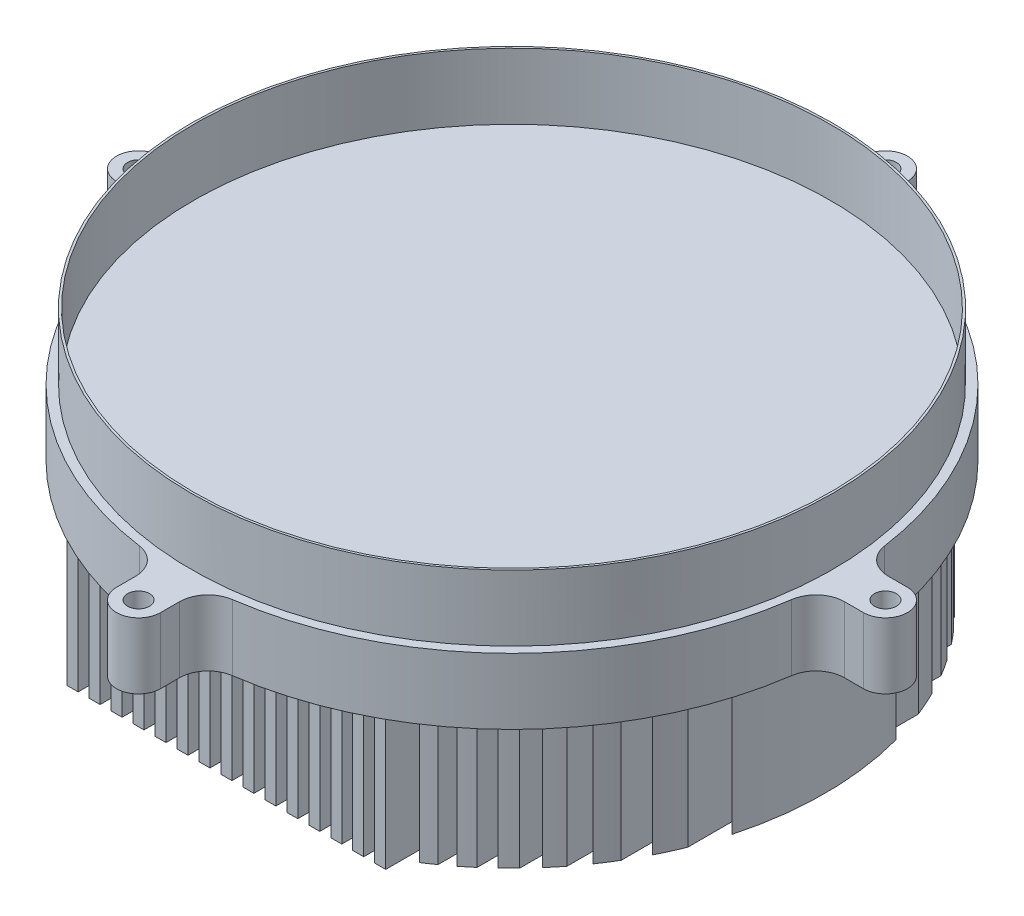
SolidWorks part; units mm, degrees
ref_plane "Front Plane" through (0, 0, 0) normal (0, 0, 1) x (1, 0, 0)
ref_plane "Top Plane" through (0, 0, 0) normal (0, 1, 0) x (1, 0, 0)
ref_plane "Right Plane" through (0, 0, 0) normal (1, 0, 0) x (0, 0, -1)
sketch "Sketch2" plane through (0, 0, 0) normal (0, 1, 0) x (1, 0, 0)
  line L0 (0, 0) -> (0, -224.3017) construction
  line L1 (0, 0) -> (0, 200) construction
  line L2 (0, 0) -> (207.2583, 0) construction
  line L3 (0, 0) -> (-200, 0) construction
  line L4 (20, 148.6607) -> (20, 168.6607)
  line L5 (-20, 148.6607) -> (-20, 168.6607)
  line L6 (148.6607, 20) -> (168.6607, 20)
  line L7 (148.6607, -20) -> (168.6607, -20)
  line L8 (20, -148.6607) -> (20, -168.6607)
  line L9 (-20, -148.6607) -> (-20, -168.6607)
  line L10 (-148.6607, -20) -> (-168.6607, -20)
  line L11 (-148.6607, 20) -> (-168.6607, 20)
  circle A0 centre (0, 0) radius 146
  circle A1 centre (0, 0) radius 145
  arc A3 (-20, 168.6607) -> (20, 168.6607) centre (0, 168.6607) cw
  circle A4 centre (0, 168.6607) radius 4.3737
  arc A5 (168.6607, 20) -> (168.6607, -20) centre (168.6607, 0) cw
  circle A6 centre (168.6607, 0) radius 4.3737
  arc A7 (20, -168.6607) -> (-20, -168.6607) centre (0, -168.6607) cw
  circle A8 centre (0, -168.6607) radius 4.3737
  arc A9 (-168.6607, -20) -> (-168.6607, 20) centre (-168.6607, 0) cw
  circle A10 centre (-168.6607, 0) radius 4.3737
  point P36 (0, 0)
  dimension "D1" = 290
  dimension "D2" = 292
  dimension "D4" = 4
extrude "Boss-Extrude2" add sketch "Sketch2" along normal blind 30 contours A1 | A0
sketch "Sketch3" plane through (0, 0, 0) normal (0, 1, 0) x (1, 0, 0)
  line L0 (0, 0) -> (211.9111, 0) construction
  line L1 (0, 0) -> (-205.2426, 0) construction
  line L2 (0, 0) -> (0, 170) construction
  line L3 (0, 0) -> (0, -200) construction
  line L4 (161.3691, 10) -> (170, 10)
  line L5 (161.3691, -10) -> (170, -10)
  line L6 (-10, 161.3691) -> (-10, 170)
  line L7 (10, 161.3691) -> (10, 170)
  line L8 (10, -161.3691) -> (10, -170)
  line L9 (-10, -161.3691) -> (-10, -170)
  line L10 (-161.3691, -10) -> (-170, -10)
  line L11 (-161.3691, 10) -> (-170, 10)
  arc A0 (-21.1656, 148.4992) -> (-148.4992, 21.1656) centre (0, 0) ccw
  circle A1 centre (0, 170) radius 5
  arc A2 (-10, 170) -> (10, 170) centre (0, 170) cw
  arc A3 (10, 161.3691) -> (21.1656, 148.4992) centre (23, 161.3691) ccw
  arc A4 (-10, 161.3691) -> (-21.1656, 148.4992) centre (-23, 161.3691) cw
  arc A5 (170, 10) -> (170, -10) centre (170, 0) cw
  arc A6 (161.3691, 10) -> (148.4992, 21.1656) centre (161.3691, 23) cw
  circle A7 centre (170, 0) radius 5
  arc A8 (161.3691, -10) -> (148.4992, -21.1656) centre (161.3691, -23) ccw
  arc A9 (10, -170) -> (-10, -170) centre (0, -170) cw
  arc A10 (10, -161.3691) -> (21.1656, -148.4992) centre (23, -161.3691) cw
  circle A11 centre (0, -170) radius 5
  arc A12 (-10, -161.3691) -> (-21.1656, -148.4992) centre (-23, -161.3691) ccw
  arc A13 (-170, -10) -> (-170, 10) centre (-170, 0) cw
  arc A14 (-161.3691, -10) -> (-148.4992, -21.1656) centre (-161.3691, -23) cw
  circle A15 centre (-170, 0) radius 5
  arc A16 (-161.3691, 10) -> (-148.4992, 21.1656) centre (-161.3691, 23) ccw
  arc A17 (-148.4992, -21.1656) -> (-21.1656, -148.4992) centre (0, 0) ccw
  arc A18 (148.4992, 21.1656) -> (21.1656, 148.4992) centre (0, 0) ccw
  arc A19 (21.1656, -148.4992) -> (148.4992, -21.1656) centre (0, 0) ccw
  point P53 (0, 0)
  dimension "D1" = 300
  dimension "D4" = 10
  dimension "D2" = 4
extrude "Boss-Extrude4" add sketch "Sketch3" against normal blind 30
sketch "Sketch4" plane through (0, -30, 0) normal (0, 1, 0) x (1, 0, 0)
  line L0 (0, 0) -> (0, 214.2399) construction
  line L1 (0, 0) -> (0, -238.4864) construction
  line L2 (0, 0) -> (-208.9775, 0) construction
  line L3 (0, 0) -> (218.7408, 0) construction
  line L4 (2.5, 130) -> (-2.5, 130)
  line L5 (-2.5, 130) -> (-2.5, -130)
  line L6 (2.5, 130) -> (2.5, -130)
  line L7 (2.5, -130) -> (-2.5, -130)
  line L8 (12.5, 130) -> (12.5, -130)
  line L9 (12.5, 130) -> (7.5, 130)
  line L10 (7.5, 130) -> (7.5, -130)
  line L11 (12.5, -130) -> (7.5, -130)
  line L12 (22.5, 130) -> (22.5, -130)
  line L13 (22.5, 130) -> (17.5, 130)
  line L14 (17.5, 130) -> (17.5, -130)
  line L15 (22.5, -130) -> (17.5, -130)
  line L16 (32.5, 130) -> (32.5, -130)
  line L17 (32.5, 130) -> (27.5, 130)
  line L18 (27.5, 130) -> (27.5, -130)
  line L19 (32.5, -130) -> (27.5, -130)
  line L20 (42.5, 130) -> (42.5, -130)
  line L21 (42.5, 130) -> (37.5, 130)
  line L22 (37.5, 130) -> (37.5, -130)
  line L23 (42.5, -130) -> (37.5, -130)
  line L24 (52.5, 130) -> (52.5, -130)
  line L25 (52.5, 130) -> (47.5, 130)
  line L26 (47.5, 130) -> (47.5, -130)
  line L27 (52.5, -130) -> (47.5, -130)
  line L28 (62.5, 130) -> (62.5, -130)
  line L29 (62.5, 130) -> (57.5, 130)
  line L30 (57.5, 130) -> (57.5, -130)
  line L31 (62.5, -130) -> (57.5, -130)
  line L32 (72.5, 130) -> (72.5, -130)
  line L33 (72.5, 130) -> (67.5, 130)
  line L34 (67.5, 130) -> (67.5, -130)
  line L35 (72.5, -130) -> (67.5, -130)
  line L36 (82.5, 116.1895) -> (82.5, -116.1895)
  line L38 (77.5, 119.5826) -> (77.5, -119.5826)
  line L40 (92.5, 108.3974) -> (92.5, -108.3974)
  line L42 (87.5, 112.4722) -> (87.5, -112.4722)
  line L44 (102.5, 98.9949) -> (102.5, -98.9949)
  line L46 (97.5, 103.923) -> (97.5, -103.923)
  line L48 (112.5, 87.4643) -> (112.5, -87.4643)
  line L50 (107.5, 93.5414) -> (107.5, -93.5414)
  line L52 (-7.5, 130) -> (-12.5, 130)
  line L53 (-12.5, 130) -> (-12.5, -130)
  line L54 (-7.5, 130) -> (-7.5, -130)
  line L55 (-7.5, -130) -> (-12.5, -130)
  line L56 (-17.5, 130) -> (-22.5, 130)
  line L57 (-22.5, 130) -> (-22.5, -130)
  line L58 (-17.5, 130) -> (-17.5, -130)
  line L59 (-17.5, -130) -> (-22.5, -130)
  line L60 (-27.5, 130) -> (-32.5, 130)
  line L61 (-32.5, 130) -> (-32.5, -130)
  line L62 (-27.5, 130) -> (-27.5, -130)
  line L63 (-27.5, -130) -> (-32.5, -130)
  line L64 (-37.5, 130) -> (-42.5, 130)
  line L65 (-42.5, 130) -> (-42.5, -130)
  line L66 (-37.5, 130) -> (-37.5, -130)
  line L67 (-37.5, -130) -> (-42.5, -130)
  line L68 (-47.5, 130) -> (-52.5, 130)
  line L69 (-52.5, 130) -> (-52.5, -130)
  line L70 (-47.5, 130) -> (-47.5, -130)
  line L71 (-47.5, -130) -> (-52.5, -130)
  line L72 (-57.5, 130) -> (-62.5, 130)
  line L73 (-62.5, 130) -> (-62.5, -130)
  line L74 (-57.5, 130) -> (-57.5, -130)
  line L75 (-57.5, -130) -> (-62.5, -130)
  line L76 (-67.5, 130) -> (-72.5, 130)
  line L77 (-72.5, 130) -> (-72.5, -130)
  line L78 (-67.5, 130) -> (-67.5, -130)
  line L79 (-67.5, -130) -> (-72.5, -130)
  line L81 (-82.5, 116.1895) -> (-82.5, -116.1895)
  line L82 (-77.5, 119.5826) -> (-77.5, -119.5826)
  line L85 (-92.5, 108.3974) -> (-92.5, -108.3974)
  line L86 (-87.5, 112.4722) -> (-87.5, -112.4722)
  line L89 (-102.5, 98.9949) -> (-102.5, -98.9949)
  line L90 (-97.5, 103.923) -> (-97.5, -103.923)
  line L93 (-112.5, 87.4643) -> (-112.5, -87.4643)
  line L94 (-107.5, 93.5414) -> (-107.5, -93.5414)
  line L97 (-122.5, 72.8011) -> (-122.5, -72.8011)
  line L98 (-117.5, 80.6226) -> (-117.5, -80.6226)
  line L101 (-132.5, 52.4404) -> (-132.5, -52.4404)
  line L102 (-127.5, 63.6396) -> (-127.5, -63.6396)
  line L106 (-137.5, 37.4166) -> (-137.5, -37.4166)
  line L108 (122.5, 72.8011) -> (122.5, -72.8011)
  line L110 (117.5, 80.6226) -> (117.5, -80.6226)
  line L112 (132.5, 52.4404) -> (132.5, -52.4404)
  line L114 (127.5, 63.6396) -> (127.5, -63.6396)
  line L118 (137.5, 37.4166) -> (137.5, -37.4166)
  line L120 (-142.5, 130) -> (-142.5, -130) [skipped]
  line L121 (142.5, 0) -> (142.5, -130) [skipped]
  line L122 (-77.5, -130) -> (-82.5, -130) [skipped]
  line L123 (-87.5, -130) -> (-92.5, -130) [skipped]
  line L124 (-97.5, -130) -> (-102.5, -130) [skipped]
  line L125 (-107.5, -130) -> (-112.5, -130) [skipped]
  line L126 (-117.5, -130) -> (-122.5, -130) [skipped]
  line L127 (-127.5, -130) -> (-132.5, -130) [skipped]
  line L128 (-137.5, -130) -> (-142.5, -130) [skipped]
  line L129 (92.5, -130) -> (87.5, -130) [skipped]
  line L130 (102.5, -130) -> (97.5, -130) [skipped]
  line L131 (112.5, -130) -> (107.5, -130) [skipped]
  line L132 (122.5, -130) -> (117.5, -130) [skipped]
  line L133 (132.5, -130) -> (127.5, -130) [skipped]
  line L134 (142.5, -130) -> (137.5, -130) [skipped]
  line L135 (82.5, -130) -> (77.5, -130) [skipped]
  line L136 (92.5, 130) -> (87.5, 130) [skipped]
  line L137 (102.5, 130) -> (97.5, 130) [skipped]
  line L138 (112.5, 130) -> (107.5, 130) [skipped]
  line L139 (122.5, 130) -> (117.5, 130) [skipped]
  line L140 (132.5, 130) -> (127.5, 130) [skipped]
  line L141 (142.5, 130) -> (137.5, 130) [skipped]
  line L142 (82.5, 130) -> (77.5, 130) [skipped]
  line L143 (-77.5, 130) -> (-82.5, 130) [skipped]
  line L144 (-87.5, 130) -> (-92.5, 130) [skipped]
  line L145 (-97.5, 130) -> (-102.5, 130) [skipped]
  line L146 (-107.5, 130) -> (-112.5, 130) [skipped]
  line L147 (-117.5, 130) -> (-122.5, 130) [skipped]
  line L148 (-127.5, 130) -> (-132.5, 130) [skipped]
  line L149 (-137.5, 130) -> (-142.5, 130) [skipped]
  arc A0 (-137.5, 37.4166) -> (-137.5, -37.4166) centre (0, 0) ccw
  arc A1 (-127.5, 63.6396) -> (-132.5, 52.4404) centre (0, 0) ccw
  arc A2 (-117.5, 80.6226) -> (-122.5, 72.8011) centre (0, 0) ccw
  arc A3 (-132.5, -52.4404) -> (-127.5, -63.6396) centre (0, 0) ccw
  arc A4 (-122.5, -72.8011) -> (-117.5, -80.6226) centre (0, 0) ccw
  arc A5 (-112.5, -87.4643) -> (-107.5, -93.5414) centre (0, 0) ccw
  arc A6 (-102.5, -98.9949) -> (-97.5, -103.923) centre (0, 0) ccw
  arc A7 (132.5, 52.4404) -> (127.5, 63.6396) centre (0, 0) ccw
  arc A8 (122.5, 72.8011) -> (117.5, 80.6226) centre (0, 0) ccw
  arc A9 (112.5, 87.4643) -> (107.5, 93.5414) centre (0, 0) ccw
  arc A10 (102.5, 98.9949) -> (97.5, 103.923) centre (0, 0) ccw
  arc A11 (92.5, 108.3974) -> (87.5, 112.4722) centre (0, 0) ccw
  arc A12 (82.5, 116.1895) -> (77.5, 119.5826) centre (0, 0) ccw
  arc A13 (-77.5, 119.5826) -> (-82.5, 116.1895) centre (0, 0) ccw
  arc A15 (-87.5, 112.4722) -> (-92.5, 108.3974) centre (0, 0) ccw
  arc A16 (-97.5, 103.923) -> (-102.5, 98.9949) centre (0, 0) ccw
  arc A17 (-107.5, 93.5414) -> (-112.5, 87.4643) centre (0, 0) ccw
  arc A19 (-82.5, -116.1895) -> (-77.5, -119.5826) centre (0, 0) ccw
  arc A20 (-92.5, -108.3974) -> (-87.5, -112.4722) centre (0, 0) ccw
  arc A21 (137.5, -37.4166) -> (137.5, 37.4166) centre (0, 0) ccw
  arc A22 (127.5, -63.6396) -> (132.5, -52.4404) centre (0, 0) ccw
  arc A23 (117.5, -80.6226) -> (122.5, -72.8011) centre (0, 0) ccw
  arc A24 (107.5, -93.5414) -> (112.5, -87.4643) centre (0, 0) ccw
  arc A25 (97.5, -103.923) -> (102.5, -98.9949) centre (0, 0) ccw
  arc A26 (87.5, -112.4722) -> (92.5, -108.3974) centre (0, 0) ccw
  arc A27 (77.5, -119.5826) -> (82.5, -116.1895) centre (0, 0) ccw
  dimension "D1" = 130
  dimension "D2" = 2.5
  dimension "D3" = 2.5
  dimension "D4" = 130
  dimension "D5" = 15
  dimension "D6" = 15
extrude "Boss-Extrude5" add sketch "Sketch4" against normal blind 60
